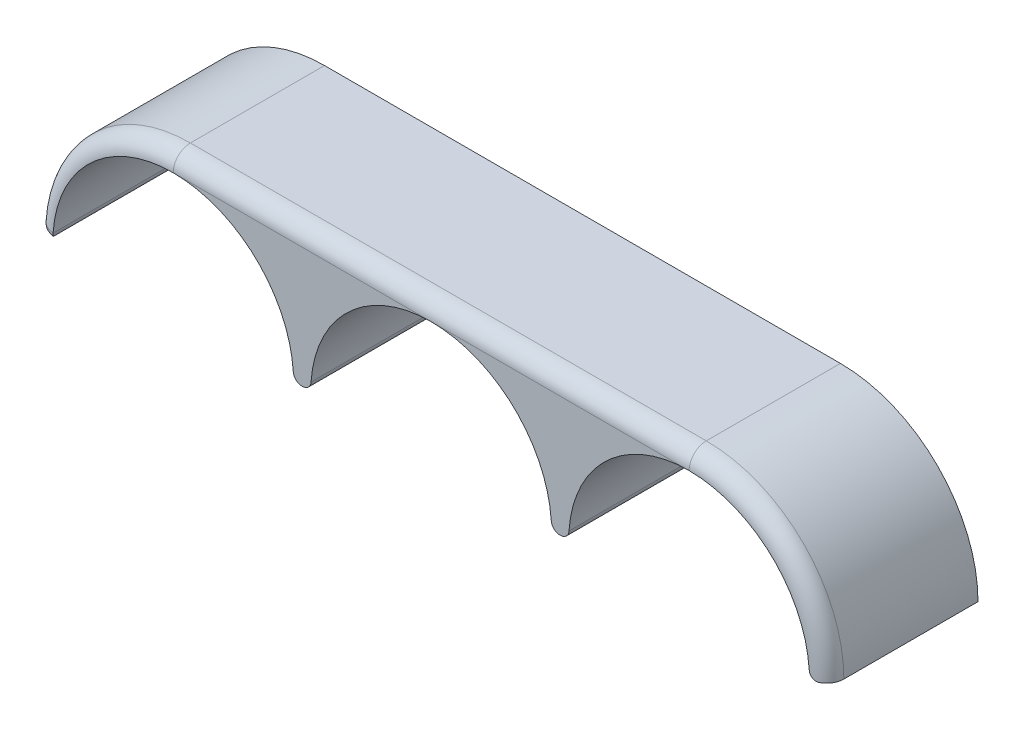
SolidWorks part; units mm, degrees
ref_plane "Plan de face" through (0, 0, 0) normal (0, 0, 1) x (1, 0, 0)
ref_plane "Plan de dessus" through (0, 0, 0) normal (0, 1, 0) x (1, 0, 0)
ref_plane "Plan de droite" through (0, 0, 0) normal (1, 0, 0) x (0, 0, -1)
sketch "Esquisse1" plane through (0, 0, 0) normal (0, 0, 1) x (1, 0, 0)
  line L0 (-220, 0) -> (220, 0) construction
  line L1 (-220, 0) -> (-230, 0)
  line L2 (220, 0) -> (230, 0)
  line L3 (-150, 80) -> (150, 80)
  line L4 (-80, 0) -> (-70, 0)
  line L5 (70, 0) -> (80, 0)
  circle A0 centre (0, 0) radius 70 construction
  circle A1 centre (150, 0) radius 70 construction
  circle A2 centre (-150, 0) radius 70 construction
  arc A3 (-220, 0) -> (-80, 0) centre (-150, 0) cw
  arc A4 (-70, 0) -> (70, 0) centre (0, 0) cw
  arc A5 (80, 0) -> (220, 0) centre (150, 0) cw
  arc A6 (-230, 0) -> (-150, 80) centre (-150, 0) cw
  arc A7 (230, 0) -> (150, 80) centre (150, 0) ccw
  dimension "D3" = 140
  dimension "D1" = 150
  dimension "D2" = 150
  dimension "D4" = 10
extrude "Boss.-Extru.1" add sketch "Esquisse1" along normal blind 88
fillet "Congé1" radius 10 3 edges at (206.5685, 56.5685, 88) (-206.5685, 56.5685, 88) (0, 80, 88)
fillet "Congé2" radius 5 8 edges at (-227.0711, 0, 85.0711) (-230, 0, 39) (-220, 0, 44) (-80, 0, 44) (-70, 0, 44) (70, 0, 44) (80, 0, 44) (220, 0, 44)
